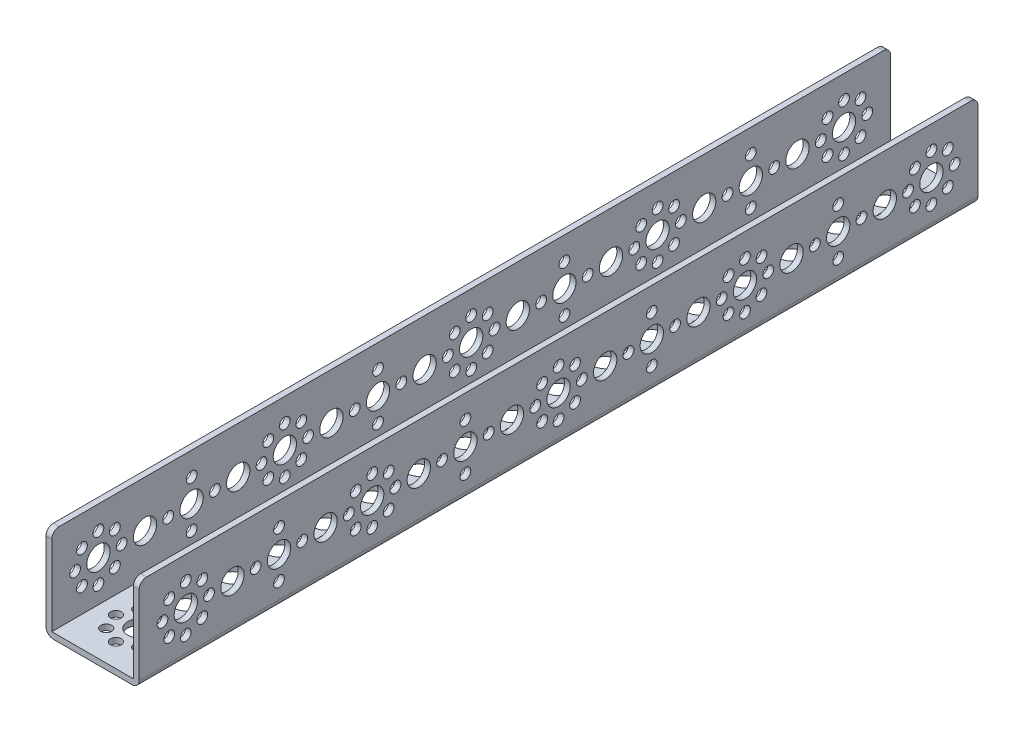
SolidWorks part; units mm, degrees
material "2024 Alloy"
ref_plane "Front Plane" through (0, 0, 0) normal (0, 0, 1) x (1, 0, 0)
ref_plane "Top Plane" through (0, 0, 0) normal (0, 1, 0) x (1, 0, 0)
ref_plane "Right Plane" through (0, 0, 0) normal (1, 0, 0) x (0, 0, -1)
ref_plane "Plane1" through (16, 0, 0) normal (1, 0, 0) x (0, 0, -1)
sketch "Sketch1" plane through (16, 0, 0) normal (1, 0, 0) x (0, 0, -1)
  line L0 (-16, 32) -> (-16, 0)
  line L1 (-16, 0) -> (272, 0)
  line L2 (272, 0) -> (272, 32)
  line L3 (272, 32) -> (-16, 32)
extrude "Boss-Extrude1" add sketch "Sketch1" against normal blind 32
sketch "Sketch2" plane through (0, 0, -272) normal (0, 0, -1) x (-1, 0, 0)
  line L0 (14, 32) -> (-14, 32)
  line L1 (-14, 32) -> (-14, 2)
  line L2 (-14, 2) -> (14, 2)
  line L3 (14, 2) -> (14, 32)
extrude "Cut-Extrude1" cut sketch "Sketch2" against normal through all
hole_wizard "Ø8.0 (8) Diameter Hole1" positions "Sketch4" profile "Sketch3" hole size "Ø8.0" standard "ANSI Metric"
sketch "Sketch4" plane through (-16, 0, 0) normal (-1, 0, 0) x (0, 0, 1)
  point P0 (-64, 16)
  point P1 (-128, 16)
  point P2 (-192, 16)
  point P3 (-256, 16)
  point P4 (-32, 16)
  point P5 (-96, 16)
  point P6 (-160, 16)
  point P7 (-224, 16)
  point P8 (-16, 16)
  point P9 (-48, 16)
  point P10 (-80, 16)
  point P11 (-112, 16)
  point P12 (0, 16)
  point P13 (-144, 16)
  point P14 (-176, 16)
  point P15 (-208, 16)
  point P16 (-240, 16)
sketch "Sketch3" plane through (-16, 16, -64) normal (0, 1, 0) x (0, 0, 1)
  line L0 (0, 0) -> (0, 2)
  line L1 (0, 2) -> (4, 2)
  line L2 (4, 2) -> (4, 0)
  line L5 (4, 0) -> (0, 0)
  line L11 (0, -6.35) -> (0, 107.95) construction
  dimension "Thru Hole Dia." = 8
  dimension "Thru Hole Depth" = 2
hole_wizard "Ø3.7 (3.7) Diameter Hole1" positions "Sketch6" profile "Sketch5" hole size "Ø3.7" standard "ANSI Metric"
sketch "Sketch6" plane through (-16, 0, 0) normal (-1, 0, 0) x (0, 0, 1)
  point P0 (0, 24)
  point P1 (0, 8)
  point P2 (-8, 16)
  point P3 (8, 16)
  point P4 (-5.6569, 21.6569)
  point P5 (5.6569, 21.6569)
  point P6 (5.6569, 10.3431)
  point P7 (-5.6569, 10.3431)
  point P8 (-64, 24)
  point P9 (-64, 8)
  point P10 (-72, 16)
  point P11 (-56, 16)
  point P12 (-69.6569, 21.6569)
  point P13 (-58.3431, 21.6569)
  point P14 (-58.3431, 10.3431)
  point P15 (-69.6569, 10.3431)
  point P16 (-128, 24)
  point P17 (-128, 8)
  point P18 (-136, 16)
  point P19 (-120, 16)
  point P20 (-133.6569, 21.6569)
  point P21 (-122.3431, 21.6569)
  point P22 (-122.3431, 10.3431)
  point P23 (-133.6569, 10.3431)
  point P24 (-192, 24)
  point P25 (-192, 8)
  point P26 (-200, 16)
  point P27 (-184, 16)
  point P28 (-197.6569, 21.6569)
  point P29 (-186.3431, 21.6569)
  point P30 (-186.3431, 10.3431)
  point P31 (-197.6569, 10.3431)
  point P32 (-256, 24)
  point P33 (-256, 8)
  point P34 (-264, 16)
  point P35 (-248, 16)
  point P36 (-261.6569, 21.6569)
  point P37 (-250.3431, 21.6569)
  point P38 (-250.3431, 10.3431)
  point P39 (-261.6569, 10.3431)
  point P40 (-32, 24)
  point P41 (-40, 16)
  point P42 (-32, 8)
  point P43 (-24, 16)
  point P44 (-96, 24)
  point P45 (-104, 16)
  point P46 (-96, 8)
  point P47 (-88, 16)
  point P48 (-160, 24)
  point P49 (-168, 16)
  point P50 (-160, 8)
  point P51 (-152, 16)
  point P52 (-224, 24)
  point P53 (-232, 16)
  point P54 (-224, 8)
  point P55 (-216, 16)
sketch "Sketch5" plane through (-16, 24, 0) normal (0, 1, 0) x (0, 0, 1)
  line L0 (0, 0) -> (0, 2)
  line L1 (0, 2) -> (1.85, 2)
  line L2 (1.85, 2) -> (1.85, 0)
  line L5 (1.85, 0) -> (0, 0)
  line L11 (0, -6.35) -> (0, 107.95) construction
  dimension "Thru Hole Dia." = 3.7
  dimension "Thru Hole Depth" = 2
hole_wizard "Ø3.7 (3.7) Diameter Hole2" positions "Sketch8" profile "Sketch7" hole size "Ø3.7" standard "ANSI Metric"
sketch "Sketch8" plane through (0, 0, 0) normal (0, -1, 0) x (-1, 0, 0)
  point P0 (8, 0)
  point P1 (5.6569, 5.6569)
  point P2 (0, 8)
  point P3 (-5.6569, 5.6569)
  point P4 (-8, 0)
  point P5 (-5.6569, -5.6569)
  point P6 (0, -8)
  point P7 (5.6569, -5.6569)
  point P8 (8, 64)
  point P9 (5.6569, 69.6569)
  point P10 (0, 72)
  point P11 (-5.6569, 69.6569)
  point P12 (-8, 64)
  point P13 (-5.6569, 58.3431)
  point P14 (0, 56)
  point P15 (5.6569, 58.3431)
  point P16 (8, 128)
  point P17 (5.6569, 133.6569)
  point P18 (0, 136)
  point P19 (-5.6569, 133.6569)
  point P20 (-8, 128)
  point P21 (-5.6569, 122.3431)
  point P22 (0, 120)
  point P23 (5.6569, 122.3431)
  point P24 (8, 192)
  point P25 (5.6569, 197.6569)
  point P26 (0, 200)
  point P27 (-5.6569, 197.6569)
  point P28 (-8, 192)
  point P29 (-5.6569, 186.3431)
  point P30 (0, 184)
  point P31 (5.6569, 186.3431)
  point P32 (8, 256)
  point P33 (5.6569, 261.6569)
  point P34 (0, 264)
  point P35 (-5.6569, 261.6569)
  point P36 (-8, 256)
  point P37 (-5.6569, 250.3431)
  point P38 (0, 248)
  point P39 (5.6569, 250.3431)
  point P40 (8, 32)
  point P41 (0, 40)
  point P42 (-8, 32)
  point P43 (0, 24)
  point P44 (8, 96)
  point P45 (0, 104)
  point P46 (-8, 96)
  point P47 (0, 88)
  point P48 (8, 160)
  point P49 (0, 168)
  point P50 (-8, 160)
  point P51 (0, 152)
  point P52 (8, 224)
  point P53 (0, 232)
  point P54 (-8, 224)
  point P55 (0, 216)
sketch "Sketch7" plane through (-8, 0, 0) normal (1, 0, 0) x (0, 0, -1)
  line L0 (0, 0) -> (0, 32)
  line L1 (0, 32) -> (1.85, 32)
  line L2 (1.85, 32) -> (1.85, 0)
  line L5 (1.85, 0) -> (0, 0)
  line L11 (0, -6.35) -> (0, 107.95) construction
  dimension "Thru Hole Dia." = 3.7
  dimension "Thru Hole Depth" = 32
hole_wizard "Ø8.0 (8) Diameter Hole2" positions "Sketch10" profile "Sketch9" hole size "Ø8.0" standard "ANSI Metric"
sketch "Sketch10" plane through (0, 0, 0) normal (0, -1, 0) x (-1, 0, 0)
  point P0 (0, 0)
  point P1 (0, 64)
  point P2 (0, 128)
  point P3 (0, 192)
  point P4 (0, 256)
  point P5 (0, 32)
  point P6 (0, 96)
  point P7 (0, 160)
  point P8 (0, 224)
  point P9 (0, 16)
  point P10 (0, 48)
  point P11 (0, 80)
  point P12 (0, 112)
  point P13 (0, 144)
  point P14 (0, 176)
  point P15 (0, 208)
  point P16 (0, 240)
sketch "Sketch9" plane through (0, 0, 0) normal (1, 0, 0) x (0, 0, -1)
  line L0 (0, 0) -> (0, 32)
  line L1 (0, 32) -> (4, 32)
  line L2 (4, 32) -> (4, 0)
  line L5 (4, 0) -> (0, 0)
  line L11 (0, -6.35) -> (0, 107.95) construction
  dimension "Thru Hole Dia." = 8
  dimension "Thru Hole Depth" = 32
hole_wizard "Ø8.0 (8) Diameter Hole3" positions "Sketch12" profile "Sketch11" hole size "Ø8.0" standard "ANSI Metric"
sketch "Sketch12" plane through (14, 0, 0) normal (-1, 0, 0) x (0, 0, 1)
  point P0 (-32, 16)
sketch "Sketch11" plane through (14, 16, -32) normal (0, 1, 0) x (0, 0, 1)
  line L0 (0, 0) -> (0, 2)
  line L1 (0, 2) -> (4, 2)
  line L2 (4, 2) -> (4, 0)
  line L5 (4, 0) -> (0, 0)
  line L11 (0, -6.35) -> (0, 107.95) construction
  dimension "Thru Hole Dia." = 8
  dimension "Thru Hole Depth" = 2
hole_wizard "Ø8.0 (8) Diameter Hole4" positions "Sketch14" profile "Sketch13" hole size "Ø8.0" standard "ANSI Metric"
sketch "Sketch14" plane through (16, 0, 0) normal (1, 0, 0) x (0, 0, -1)
  point P0 (64, 16)
  point P1 (128, 16)
  point P2 (192, 16)
  point P3 (256, 16)
  point P4 (96, 16)
  point P5 (160, 16)
  point P6 (224, 16)
  point P7 (16, 16)
  point P8 (48, 16)
  point P9 (80, 16)
  point P10 (112, 16)
  point P11 (0, 16)
  point P12 (144, 16)
  point P13 (176, 16)
  point P14 (208, 16)
  point P15 (240, 16)
sketch "Sketch13" plane through (16, 16, -64) normal (0, 1, 0) x (0, 0, -1)
  line L0 (0, 0) -> (0, 32)
  line L1 (0, 32) -> (4, 32)
  line L2 (4, 32) -> (4, 0)
  line L5 (4, 0) -> (0, 0)
  line L11 (0, -6.35) -> (0, 107.95) construction
  dimension "Thru Hole Dia." = 8
  dimension "Thru Hole Depth" = 32
hole_wizard "Ø3.7 (3.7) Diameter Hole3" positions "Sketch16" profile "Sketch15" hole size "Ø3.7" standard "ANSI Metric"
sketch "Sketch16" plane through (16, 0, 0) normal (1, 0, 0) x (0, 0, -1)
  point P0 (0, 24)
  point P1 (0, 8)
  point P2 (8, 16)
  point P3 (-8, 16)
  point P4 (5.6569, 21.6569)
  point P5 (-5.6569, 21.6569)
  point P6 (-5.6569, 10.3431)
  point P7 (5.6569, 10.3431)
  point P8 (64, 24)
  point P9 (64, 8)
  point P10 (72, 16)
  point P11 (56, 16)
  point P12 (69.6569, 21.6569)
  point P13 (58.3431, 21.6569)
  point P14 (58.3431, 10.3431)
  point P15 (69.6569, 10.3431)
  point P16 (128, 24)
  point P17 (128, 8)
  point P18 (136, 16)
  point P19 (120, 16)
  point P20 (133.6569, 21.6569)
  point P21 (122.3431, 21.6569)
  point P22 (122.3431, 10.3431)
  point P23 (133.6569, 10.3431)
  point P24 (192, 24)
  point P25 (192, 8)
  point P26 (200, 16)
  point P27 (184, 16)
  point P28 (197.6569, 21.6569)
  point P29 (186.3431, 21.6569)
  point P30 (186.3431, 10.3431)
  point P31 (197.6569, 10.3431)
  point P32 (256, 24)
  point P33 (256, 8)
  point P34 (264, 16)
  point P35 (248, 16)
  point P36 (261.6569, 21.6569)
  point P37 (250.3431, 21.6569)
  point P38 (250.3431, 10.3431)
  point P39 (261.6569, 10.3431)
  point P40 (32, 24)
  point P41 (40, 16)
  point P42 (32, 8)
  point P43 (24, 16)
  point P44 (96, 24)
  point P45 (104, 16)
  point P46 (96, 8)
  point P47 (88, 16)
  point P48 (160, 24)
  point P49 (168, 16)
  point P50 (160, 8)
  point P51 (152, 16)
  point P52 (224, 24)
  point P53 (232, 16)
  point P54 (224, 8)
  point P55 (216, 16)
sketch "Sketch15" plane through (16, 24, 0) normal (0, 1, 0) x (0, 0, -1)
  line L0 (0, 0) -> (0, 32)
  line L1 (0, 32) -> (1.85, 32)
  line L2 (1.85, 32) -> (1.85, 0)
  line L5 (1.85, 0) -> (0, 0)
  line L11 (0, -6.35) -> (0, 107.95) construction
  dimension "Thru Hole Dia." = 3.7
  dimension "Thru Hole Depth" = 32
fillet "Fillet1" radius 2.5 6 edges at (-16, 0, -128) (-15, 32, -272) (-15, 32, 16) (16, 0, -128) (15, 32, 16) (15, 32, -272) tangent propagation no
